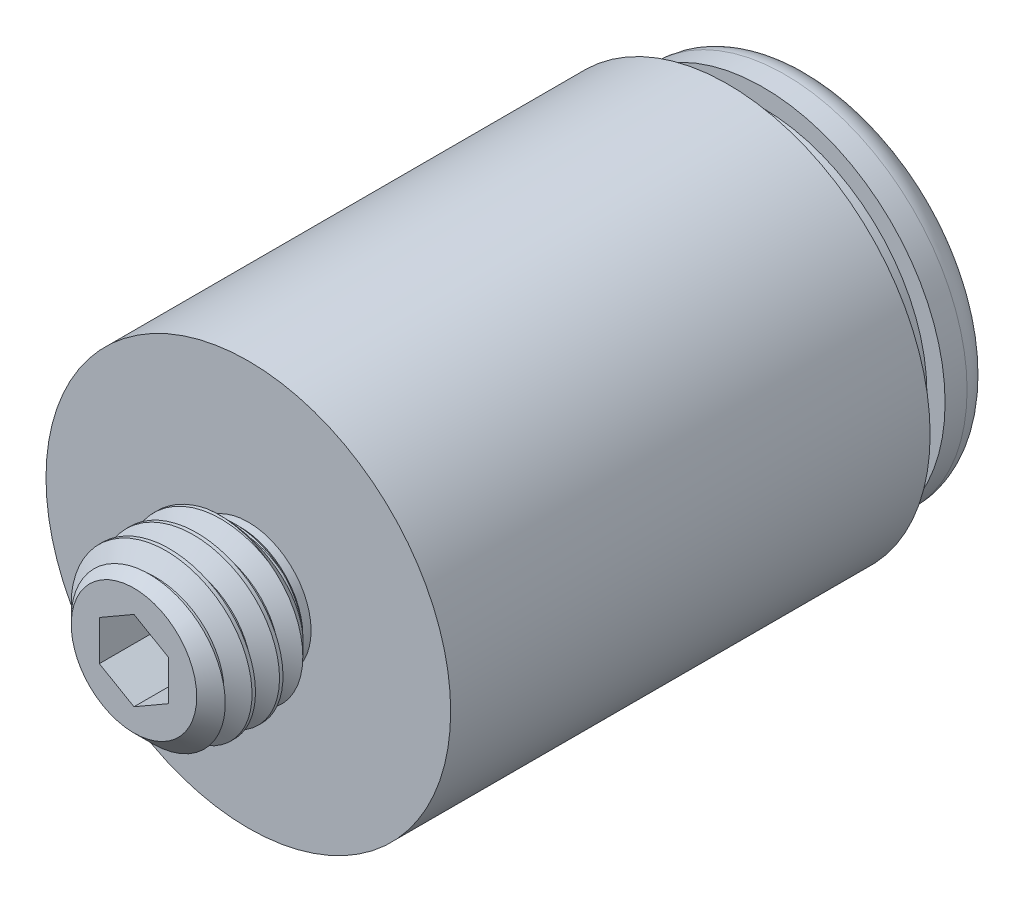
SolidWorks part; units mm, degrees
ref_plane "Front Plane" through (0, 0, 0) normal (0, 0, 1) x (1, 0, 0)
ref_plane "Top Plane" through (0, 0, 0) normal (0, 1, 0) x (1, 0, 0)
ref_plane "Right Plane" through (0, 0, 0) normal (1, 0, 0) x (0, 0, -1)
sketch "Sketch1" plane through (0, 0, 0) normal (0, 0, 1) x (1, 0, 0)
  circle A0 centre (0, 0) radius 2.413
  dimension "pipe od" = 4.826
extrude "Extrude1" add sketch "Sketch1" against normal blind 3.302
sketch "Sketch2" plane through (0, 0, 0) normal (0, 0, 1) x (1, 0, 0)
  circle A0 centre (0, 0) radius 2.413 construction
  circle A1 centre (0, 0) radius 2.413
  point P4 (0, 2.413)
curve "Helix/Spiral1" pitch 0.7937 height 5.334 turns 6.72 parameters "pitch"=0.7937
sketch "Sketch3" plane through (0, 0, 0) normal (1, 0, 0) x (0, 0, -1)
  line L0 (-0.6945, 2.413) -> (-0.3969, 1.8974) construction
  line L1 (-0.3969, 1.8974) -> (-0.2977, 1.8974)
  line L2 (-0.3473, 2.413) -> (-0.3473, 2.4989) construction
  line L3 (-0.6945, 2.413) -> (0, 2.413) construction
  line L4 (-0.3473, 2.413) -> (-0.3473, 1.8974) construction
  line L5 (-0.5457, 2.1552) -> (-0.1488, 2.1552) construction
  line L6 (-0.3473, 2.456) -> (-0.7193, 2.456) construction
  line L7 (-0.7193, 2.456) -> (0.0496, 2.4989)
  line L8 (0, -2.413) -> (3.302, -2.413) construction
  line L9 (0.0496, 2.4989) -> (-0.3473, 1.8115) construction
  line L10 (-0.3473, 1.8115) -> (-0.7441, 2.4989) construction
  line L11 (-0.7441, 2.4989) -> (0.0496, 2.4989) construction
  line L12 (0.0496, 2.4989) -> (-0.2977, 1.8974)
  line L13 (-0.3969, 1.8974) -> (-0.7193, 2.456)
  line L14 (-0.3473, -2.413) -> (-0.3473, 1.8115) construction
  line L15 (-0.3473, -2.413) -> (0.4465, -2.413) construction
  line L16 (0.4465, -2.413) -> (1.2402, -2.413) construction
  line L17 (1.2402, -2.413) -> (2.034, -2.413) construction
  dimension "D2" = 0.0992
  dimension "D3" = 0.3969
sweep "Cut-Sweep1" cut profiles "Sketch3" path "Helix/Spiral1"
sketch "Sketch4" plane through (0, 0, 0) normal (1, 0, 0) x (0, 0, -1)
  line L0 (0, 0) -> (3.302, 0) construction
  line L1 (3.302, 2.4989) -> (0.0496, 2.4989) construction
  line L2 (-0.3473, 1.8115) -> (3.302, 1.8115) construction
  line L5 (3.302, 1.8115) -> (3.0639, 1.8115)
  line L6 (3.0639, 1.8115) -> (2.3765, 2.4989)
  line L7 (3.302, 1.8115) -> (3.302, 2.4989)
  line L8 (3.302, 2.4989) -> (2.3765, 2.4989)
  line L9 (0.6874, 2.4989) -> (0, 1.8115)
  line L10 (0, 1.8115) -> (0, 2.4989)
  line L11 (0.6874, 2.4989) -> (0, 2.4989)
  line L12 (0, 2.413) -> (0, -2.413) construction
  line L13 (3.302, -1.9562) -> (3.302, 1.3005) construction
  dimension "D2" = 45
  dimension "D3" = 0.2381
  dimension "D4" = 45
revolve "Cut-Revolve1" cut sketch "Sketch4" angle 360 about L0
sketch "Sketch5" plane through (0, 0, -3.302) normal (0, 0, -1) x (-1, 0, 0)
  line L1 (0, 6.7458) -> (-5.842, 3.3729) construction
  line L2 (-5.842, 3.3729) -> (-5.842, -3.3729) construction
  line L3 (-5.842, -3.3729) -> (0, -6.7458) construction
  line L4 (0, -6.7458) -> (5.842, -3.3729) construction
  line L5 (5.842, -3.3729) -> (5.842, 3.3729) construction
  line L6 (5.842, 3.3729) -> (0, 6.7458) construction
  circle A0 centre (0, 0) radius 5.842
  dimension "Hex Size" = 11.684
extrude "Extrude2" add sketch "Sketch5" along normal blind 4.0894
sketch "Sketch6" plane through (0, 0, -7.3914) normal (0, 0, -1) x (-1, 0, 0)
  circle A0 centre (0, 0) radius 5.842 construction
  circle A1 centre (0, 0) radius 5.842
extrude "Cut-Extrude1" [suppressed] cut sketch "Sketch6" against normal through all draft 60 flip side to cut
sketch "Sketch7" plane through (0, 0, -3.302) normal (0, 0, 1) x (1, 0, 0)
  circle A0 centre (0, 0) radius 5.842 construction
  circle A1 centre (0, 0) radius 5.842
extrude "Cut-Extrude2" [suppressed] cut sketch "Sketch7" against normal through all draft 60 flip side to cut
sketch "Sketch8" plane through (0, 0, 0) normal (1, 0, 0) x (0, 0, -1)
  line L0 (18.161, 5.2578) -> (18.796, 5.2578)
  line L1 (7.3914, 5.842) -> (17.145, 5.842)
  line L2 (7.3914, 5.842) -> (7.3914, 3.175)
  line L3 (7.3914, 3.175) -> (19.177, 3.175)
  line L4 (19.558, 4.4958) -> (19.558, 3.556)
  line L6 (17.145, 5.842) -> (17.145, 4.732)
  line L7 (17.145, 4.732) -> (18.161, 4.732)
  line L8 (18.161, 5.2578) -> (18.161, 4.732)
  line L9 (3.302, 1.8115) -> (3.302, -1.8115) construction
  line L10 (0, 0) -> (44.9134, 0) construction
  line L12 (19.177, 3.175) -> (19.558, 3.556)
  line L13 (7.3914, -5.842) -> (7.3914, 5.842) construction
  arc A0 (18.796, 5.2578) -> (19.558, 4.4958) centre (18.796, 4.4958) cw
  point P1 (19.558, 3.175)
  point P20 (19.558, 5.2578)
  dimension "D4" = 0.762
  dimension "D1" = 1.397
  dimension "H" = 16.256
  dimension "tube od" = 6.35
  dimension "D2" = 1.016
  dimension "D3" = 9.464
  dimension "D7" = 0.381
  dimension "D5" = 11.684
  dimension "D6" = 10.5156
revolve "Revolve1" add sketch "Sketch8" angle 360 about L10
sketch "Sketch9" plane through (0, 0, -7.3914) normal (0, 0, -1) x (-1, 0, 0)
  line L1 (0, 1.1547) -> (-1, 0.5774)
  line L2 (-1, 0.5774) -> (-1, -0.5774)
  line L3 (-1, -0.5774) -> (0, -1.1547)
  line L4 (0, -1.1547) -> (1, -0.5774)
  line L5 (1, -0.5774) -> (1, 0.5774)
  line L6 (1, 0.5774) -> (0, 1.1547)
  circle A0 centre (0, 0) radius 3.175 construction
  circle A1 centre (0, 0) radius 1 construction
  circle A3 centre (0, 0) radius 1 construction
  dimension "F2" = 2
extrude "Cut-Extrude3" cut sketch "Sketch9" against normal through all
sketch "Sketch10" plane through (0, 0, -7.3914) normal (0, 0, -1) x (-1, 0, 0)
  circle A1 centre (0, 0) radius 3.175
  circle A2 centre (0, 0) radius 3.175
  dimension "D1" = 0
extrude "Cut-Extrude4" cut sketch "Sketch10" against normal offset from surface (2.5654 mm away) 1.524 up to face at (-1.8115, 0, -3.302)
sketch "Sketch11" plane through (0, 0, 0) normal (0, 0, 1) x (1, 0, 0)
  circle A1 centre (0, 0) radius 0.7955
  circle A2 centre (0, 0) radius 0.7955
  dimension "D1" = 1.016
extrude "Cut-Extrude5" [suppressed] cut sketch "Sketch11" against normal offset from surface (2.794 mm away) 2.032
equation "\"D3@Helix/Spiral1\" = \"Thread length@Extrude1\"+.08"
equation "\"D2@Sketch3\" = \"pitch@Helix/Spiral1\"*.125"
equation "\"D3@Sketch3\" = \"pitch@Helix/Spiral1\"*.5"
equation "\"D3@Sketch4\" = \"pitch@Helix/Spiral1\"*.3"
equation "\"D1@Extrude2\" = \"Hex Size@Sketch5\"*.35"
equation "\"D5@Sketch8\" = \"Hex Size@Sketch5\""
equation "\"D6@Sketch8\" = \"D5@Sketch8\"*.9"
equation "\"D3@Sketch8\" = \"D6@Sketch8\"*.9"
